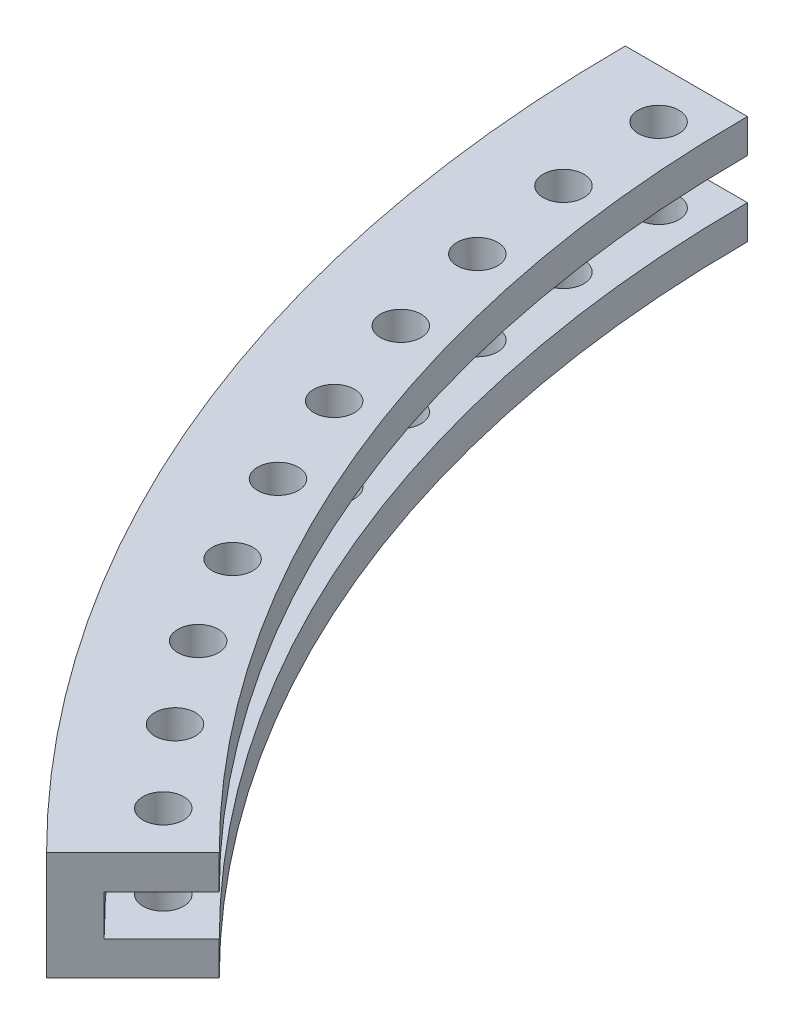
SolidWorks part; units mm, degrees
ref_plane "Front Plane" through (0, 0, 0) normal (0, 0, 1) x (1, 0, 0)
ref_plane "Top Plane" through (0, 0, 0) normal (0, 1, 0) x (1, 0, 0)
ref_plane "Right Plane" through (0, 0, 0) normal (1, 0, 0) x (0, 0, -1)
ref_axis "Axe1" through (0, -55, 0) along (0, 1, 0)
sketch "Esquisse2" plane through (0, 0, 0) normal (0, 0, 1) x (1, 0, 0)
  line L0 (-103, 4) -> (-103, -4)
  line L1 (-103, -4) -> (-94, -4)
  line L2 (-94, -4) -> (-94, -1.5)
  line L3 (-94, -1.5) -> (-100, -1.5)
  line L4 (-100, -1.5) -> (-100, 1.5)
  line L5 (-100, 1.5) -> (-94, 1.5)
  line L6 (-94, 1.5) -> (-94, 4)
  line L7 (-94, 4) -> (-103, 4)
  line L9 (0, -55) -> (0, 55) construction
  point P2 (-100, 0)
  dimension "D1" = 100
  dimension "D2" = 3
  dimension "D3" = 3
  dimension "D4" = 8
  dimension "D5" = 6
  dimension "D6" = 94
revolve "Révolution1" add sketch "Esquisse2" angle 45 about axis through (0, -55, 0) along (0, 1, 0)
sketch "Esquisse3" plane through (0, 4, 0) normal (0, 1, 0) x (1, 0, 0)
  line L0 (-66.468, -66.468) -> (-72.832, -72.832) construction
  circle A0 centre (-71.3594, -65.7026) radius 1.5
  dimension "D1" = 3
  dimension "D2" = 97
  dimension "D3" = 4
extrude "Enlèv. mat.-Extru.1" cut sketch "Esquisse3" against normal through all
pattern_circular "Répétition circulaire1" count 10 every 4.5 about axis through (0, -55, 0) along (0, 1, 0) of "Enlèv. mat.-Extru.1" reverse direction yes
